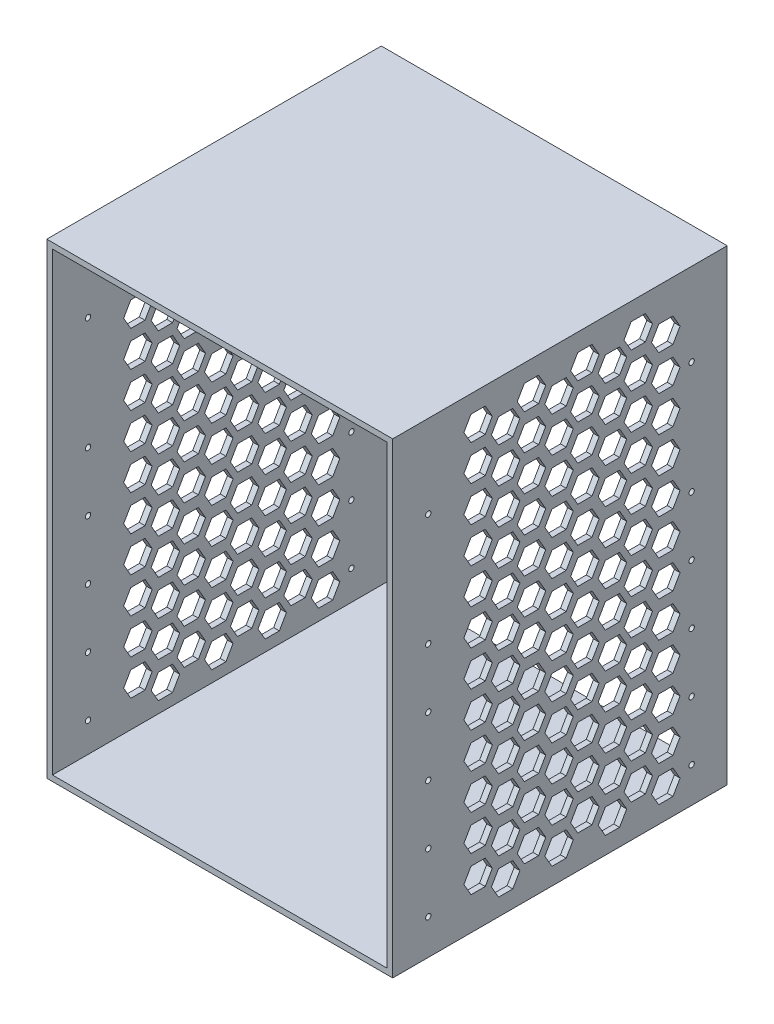
SolidWorks part; units mm, degrees
ref_plane "Front Plane" through (0, 0, 0) normal (0, 0, 1) x (1, 0, 0)
ref_plane "Top Plane" through (0, 0, 0) normal (0, 1, 0) x (1, 0, 0)
ref_plane "Right Plane" through (0, 0, 0) normal (1, 0, 0) x (0, 0, -1)
sketch "Sketch1" plane through (0, 0, 0) normal (0, 0, 1) x (1, 0, 0)
  line L0 (-42.695, 26.84) -> (51.305, 26.84)
  line L1 (51.305, 26.84) -> (51.305, -101.16)
  line L2 (51.305, -101.16) -> (-42.695, -101.16)
  line L3 (-42.695, -101.16) -> (-42.695, 26.84)
  line L5 (-44.295, 28.44) -> (52.905, 28.44)
  line L6 (-44.295, 28.44) -> (-44.295, -102.76)
  line L7 (-44.295, -102.76) -> (52.905, -102.76)
  line L8 (52.905, 28.44) -> (52.905, -102.76)
  dimension "D1" = 94
  dimension "D2" = 128
  dimension "D3" = 1.6
  dimension "D4" = 1.6
  dimension "D5" = 1.6
  dimension "D6" = 1.6
extrude "Boss-Extrude1" add sketch "Sketch1" along normal blind 94
sketch "Sketch2" plane through (52.905, 0, 0) normal (1, 0, 0) x (0, 0, -1)
  line L0 (-94, 28.44) -> (-94, -102.76)
  line L1 (-94, 28.44) -> (0, 28.44) construction
  line L2 (-94, -102.76) -> (-94, 28.44) construction
  line L3 (-94, -102.76) -> (0, -102.76) construction
  line L4 (-94, -84.56) -> (0, -84.56) construction
  line L5 (0, -102.76) -> (0, 28.44) construction
  line L6 (-94, -67.96) -> (0, -67.96) construction
  line L7 (-94, -51.36) -> (0, -51.36) construction
  line L8 (-94, -34.76) -> (0, -34.76) construction
  line L9 (-94, -3.16) -> (0, -3.16) construction
  line L10 (-94, -43.06) -> (0, -43.06)
  line L11 (-94, -59.66) -> (0, -59.66)
  line L12 (-94, -76.26) -> (0, -76.26)
  line L13 (-94, -92.86) -> (0, -92.86)
  line L14 (-94, -26.46) -> (0, -26.46)
  line L15 (-94, 5.14) -> (0, 5.14)
  line L16 (-94, -11.46) -> (0, -11.46)
  line L17 (-94, -83.76) -> (0, -83.76)
  line L18 (0, -83.76) -> (0, -85.36)
  line L19 (0, -85.36) -> (-94, -85.36)
  line L20 (-94, -67.16) -> (0, -67.16)
  line L21 (0, -67.16) -> (0, -68.76)
  line L22 (0, -68.76) -> (-94, -68.76)
  line L23 (-94, -50.56) -> (0, -50.56)
  line L24 (0, -50.56) -> (0, -52.16)
  line L25 (0, -52.16) -> (-94, -52.16)
  line L26 (-94, -33.96) -> (0, -33.96)
  line L27 (-94, -35.56) -> (0, -35.56)
  line L29 (-94, -2.36) -> (0, -2.36)
  line L30 (0, -2.36) -> (0, -3.96)
  line L31 (0, -3.96) -> (-94, -3.96)
  circle A11 centre (-84, 5.14) radius 0.75
  circle A13 centre (-84, -26.46) radius 0.75
  circle A14 centre (-84, -43.06) radius 0.75
  circle A15 centre (-84, -59.66) radius 0.75
  circle A16 centre (-84, -76.26) radius 0.75
  circle A17 centre (-84, -92.86) radius 0.75
  circle A18 centre (-10, 5.14) radius 0.75
  circle A20 centre (-10, -26.46) radius 0.75
  circle A21 centre (-10, -43.06) radius 0.75
  circle A22 centre (-10, -59.66) radius 0.75
  circle A23 centre (-10, -76.26) radius 0.75
  circle A24 centre (-10, -92.86) radius 0.75
  circle A25 centre (-84, -11.46) radius 0.75
  circle A26 centre (-10, -11.46) radius 0.75
  dimension "D7" = 23.3
  dimension "D8" = 23.3
  dimension "D9" = 8.3
  dimension "D10" = 8.3
  dimension "D11" = 8.3
  dimension "D12" = 8.3
  dimension "D13" = 1.5
  dimension "D14" = 10
  dimension "D15" = 10
  dimension "D16" = 1.5
  dimension "D17" = 1.5
  dimension "D18" = 1.5
  dimension "D19" = 1.5
  dimension "D20" = 1.5
  dimension "D21" = 1.5
  dimension "D22" = 1.5
  dimension "D23" = 1.5
  dimension "D24" = 1.5
  dimension "D25" = 1.5
  dimension "D26" = 1.5
  dimension "D1" = 18.2
  dimension "D2" = 16.6
  dimension "D3" = 16.6
  dimension "D4" = 16.6
  dimension "D5" = 31.6
  dimension "D6" = 31.6
  dimension "D27" = 8.3
  dimension "D28" = 0.8
  dimension "D29" = 0.8
  dimension "D30" = 0.8
  dimension "D31" = 0.8
  dimension "D32" = 0.8
  dimension "D33" = 0.8
  dimension "D34" = 0.8
  dimension "D35" = 0.8
  dimension "D36" = 0.8
  dimension "D37" = 0.8
  dimension "D38" = 7.5
extrude "Cut-Extrude1" cut sketch "Sketch2" against normal blind 100 contours L15 A11 | L15 A11 | L15 A18 | L15 A18 | L14 A13 | L14 A13 | L10 A21 | L10 A14 | L11 A15 | L11 A22 | L11 A22 | L12 A16 | L12 A16 | L12 A23 | L13 A17 | L13 A17 | L12 A23 | L13 A24 | L13 A24 | A20 | A21 | A14 | A15 region at (52.905, -26.1417, 84) region at (52.905, -26.7783, 84) region at (52.905, -43.3783, 10) region at (52.905, -42.7417, 84) region at (52.905, -59.3417, 10) region at (52.905, -59.9783, 10) region at (52.905, -59.3417, 84) region at (52.905, -75.9417, 10) region at (52.905, -76.5783, 10) region at (52.905, -75.9417, 84) region at (52.905, -76.5783, 84) region at (52.905, -92.5417, 10) region at (52.905, -93.1783, 10) region at (52.905, -92.5417, 84) region at (52.905, -93.1783, 84) region at (52.905, 5.4583, 10) region at (52.905, 4.8217, 10) region at (52.905, 5.4583, 84) region at (52.905, 4.8217, 84)
sketch "Sketch6" plane through (52.905, 0, 0) normal (1, 0, 0) x (0, 0, -1)
  line L0 (-74, 19.9759) -> (-72, 23.44)
  line L1 (-72, 23.44) -> (-68, 23.44)
  line L2 (-68, 23.44) -> (-66, 19.9759)
  line L3 (-66, 19.9759) -> (-68, 16.5118)
  line L4 (-68, 16.5118) -> (-72, 16.5118)
  line L5 (-72, 16.5118) -> (-74, 19.9759)
  line L18 (-94, 28.44) -> (0, 28.44) construction
  line L19 (-94, -102.76) -> (-94, 28.44) construction
  line L20 (-66.2557, 15.5047) -> (-64.2557, 18.9688)
  line L21 (-64.2557, 18.9688) -> (-60.2557, 18.9688)
  line L22 (-60.2557, 18.9688) -> (-58.2557, 15.5047)
  line L23 (-58.2557, 15.5047) -> (-60.2557, 12.0406)
  line L24 (-60.2557, 12.0406) -> (-64.2557, 12.0406)
  line L25 (-64.2557, 12.0406) -> (-66.2557, 15.5047)
  dimension "D1" = 120
  dimension "D2" = 120
  dimension "D3" = 120
  dimension "D4" = 4
  dimension "D5" = 4
  dimension "D6" = 4
  dimension "D7" = 4
  dimension "D8" = 5
  dimension "D9" = 20
  dimension "D10" = 120
  dimension "D11" = 120
  dimension "D12" = 120
  dimension "D13" = 4
  dimension "D14" = 4
  dimension "D15" = 4
  dimension "D16" = 4
  dimension "D17" = 2.0142
  dimension "D18" = 2.0142
extrude "Cut-Extrude4" cut sketch "Sketch6" against normal blind 100
pattern_linear "LPattern2" count 4 spacing 15 along (0, 0, -1) count 12 spacing 10 along (0, -1, 0) of "Cut-Extrude4"
